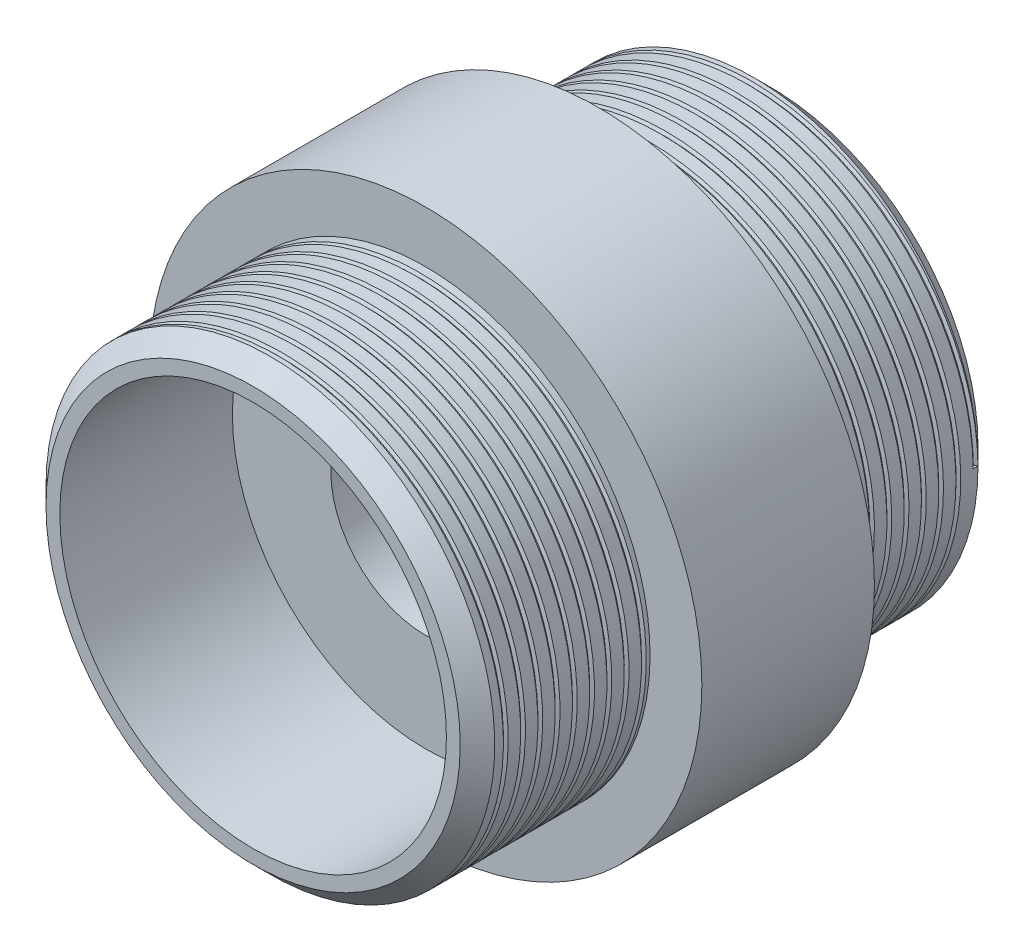
SolidWorks part; units mm, degrees
ref_plane "Ön Düzlem" through (0, 0, 0) normal (0, 0, 1) x (1, 0, 0)
ref_plane "Üst Düzlem" through (0, 0, 0) normal (0, 1, 0) x (1, 0, 0)
ref_plane "Sağ Düzlem" through (0, 0, 0) normal (1, 0, 0) x (0, 0, -1)
sketch "Çizim1" plane through (0, 0, 0) normal (0, 0, 1) x (1, 0, 0)
  circle A0 centre (0, 0) radius 13
  dimension "D1" = 26
extrude "Yükseklik-Ekstrüzyon1" add sketch "Çizim1" along normal blind 10
sketch "Çizim2" plane through (0, 0, 10) normal (0, 0, 1) x (1, 0, 0)
  circle A0 centre (0, 0) radius 16
  dimension "D1" = 32
extrude "Yükseklik-Ekstrüzyon2" add sketch "Çizim2" along normal blind 10
sketch "Çizim3" plane through (0, 0, 20) normal (0, 0, 1) x (1, 0, 0)
  circle A0 centre (0, 0) radius 13
  dimension "D1" = 26
extrude "Yükseklik-Ekstrüzyon3" add sketch "Çizim3" along normal blind 10
chamfer "Pah1" distance 1 angle 45 2 edges at (13, 0, 0) (13, 0, 30)
thread "Diş1" pitch 0.3175 method cut profile "Diş Profili1" start angle 0, offset 0, length 10, pitch 1, diameter 26
ref_plane "Düzlem1" through (13, 0, 1) normal (0, -1, 0) x (1, 0, 0)
sketch "Diş Profili1" plane through (13, 0, 1) normal (0, -1, 0) x (1, 0, 0)
  line L0 (0, 0) -> (0, 0.3175) construction
  line L11 (0, 0) -> (0, 0.2778)
  line L12 (0, 0.2778) -> (-0.1719, 0.1786)
  line L13 (-0.1719, 0.1786) -> (-0.1719, 0.0992)
  line L15 (-0.1719, 0.0992) -> (0, 0)
  line L17 (-0.1719, 0.1389) -> (0, 0.1389) construction
  point P2 (0, 0)
  dimension "Pitch" = 0.3175
  dimension "Profile_Angle" = 60
  dimension "Profile_Land" = 0.0794
  dimension "Profile_Height" = 0.1719
thread "Diş2" pitch 0.3175 method cut profile "Diş Profili2" start angle 0, offset 0, length 10, pitch 1, diameter 26
ref_plane "Düzlem2" through (-13, 0, 29) normal (0, -1, 0) x (-1, 0, 0)
sketch "Diş Profili2" plane through (-13, 0, 29) normal (0, -1, 0) x (-1, 0, 0)
  line L0 (0, 0) -> (0, 0.3175) construction
  line L11 (0, 0) -> (0, 0.2778)
  line L12 (0, 0.2778) -> (-0.1719, 0.1786)
  line L13 (-0.1719, 0.1786) -> (-0.1719, 0.0992)
  line L15 (-0.1719, 0.0992) -> (0, 0)
  line L17 (-0.1719, 0.1389) -> (0, 0.1389) construction
  point P2 (0, 0)
  dimension "Pitch" = 0.3175
  dimension "Profile_Angle" = 60
  dimension "Profile_Land" = 0.0794
  dimension "Profile_Height" = 0.1719
sketch "Çizim4" plane through (0, 0, 30) normal (0, 0, 1) x (1, 0, 0)
  circle A0 centre (0, 0) radius 11.2
  dimension "D1" = 22.4
extrude "Kes-Ekstrüzyon1" cut sketch "Çizim4" against normal blind 10
sketch "Çizim5" plane through (0, 0, 0) normal (0, 0, -1) x (-1, 0, 0)
  circle A0 centre (0, 0) radius 11.2
  dimension "D1" = 22.4
extrude "Kes-Ekstrüzyon2" cut sketch "Çizim5" against normal blind 10
sketch "Çizim6" plane through (0, 0, 10) normal (0, 0, -1) x (-1, 0, 0)
  circle A0 centre (0, 0) radius 5.5
  dimension "D1" = 11
extrude "Kes-Ekstrüzyon3" cut sketch "Çizim6" against normal blind 32
sketch "Çizim7" plane through (0, 0, 10) normal (0, 0, -1) x (-1, 0, 0)
  circle A0 centre (0, 9.7721) radius 1
  dimension "D1" = 2
extrude "Kes-Ekstrüzyon4" cut sketch "Çizim7" against normal blind 8
